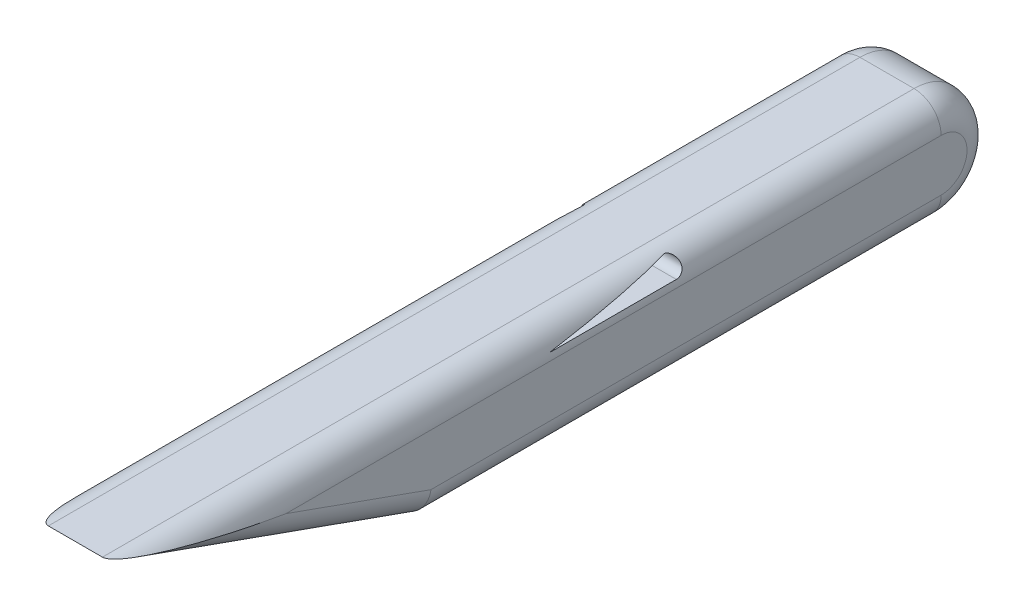
SolidWorks part; units mm, degrees
ref_plane "Front Plane" through (0, 0, 0) normal (0, 0, 1) x (1, 0, 0)
ref_plane "Top Plane" through (0, 0, 0) normal (0, 1, 0) x (1, 0, 0)
ref_plane "Right Plane" through (0, 0, 0) normal (1, 0, 0) x (0, 0, -1)
sketch "Sketch1" plane through (0, 0, 0) normal (1, 0, 0) x (0, 0, -1)
  line L0 (-537.0166, 60.4972) -> (11.6022, -135.0829)
  line L1 (11.6022, -135.0829) -> (962.9834, -135.0829)
  line L2 (-537.0166, 60.4972) -> (962.9834, 60.4972)
  arc A0 (962.9834, 60.4972) -> (962.9834, -135.0829) centre (962.9834, -37.2928) cw
  dimension "D1" = 1500
extrude "Boss-Extrude1" add sketch "Sketch1" against normal mid plane 200 contours A0 L1 L0 L2
fillet "Fillet1" radius 50 8 edges at (-100, -135.0829, -487.2928) (-100, -37.2928, -1060.7735) (100, 60.4972, -212.9834) (100, -37.2928, -1060.7735) (100, -37.2928, 262.7072) (-100, -37.2928, 262.7072) (-100, 60.4972, -212.9834) (100, -135.0829, -487.2928)
sketch "Sketch2" plane through (-100, 0, 0) normal (-1, 0, 0) x (0, 0, 1)
  line L0 (-240.2784, 23.0751) -> (-475.2168, 23.0751) construction
  line L1 (-473.2935, 53.0751) -> (-240.2784, 23.0751) construction
  line L2 (-240.2784, 23.0751) -> (-475.2168, 23.0751)
  line L3 (-473.2935, 53.0751) -> (-240.2784, 23.0751)
  arc A0 (-473.2935, 53.0751) -> (-475.2168, 23.0751) centre (-475.2168, 38.1367) ccw construction
  arc A1 (-473.2935, 53.0751) -> (-475.2168, 23.0751) centre (-475.2168, 38.1367) ccw
extrude "Cut-Extrude1" cut sketch "Sketch2" against normal blind 300
sketch "Sketch3" plane through (0, -135.0829, 0) normal (0, -1, 0) x (1, 0, 0)
  line L0 (50, -962.9834) -> (50, -11.6022) construction
  line L1 (-50, -962.9834) -> (50, -962.9834)
  line L2 (-50, -962.9834) -> (-50, 537.0166)
  line L3 (-50, 537.0166) -> (50, 537.0166)
  line L4 (50, -962.9834) -> (50, 537.0166)
  line L5 (-50, 537.0166) -> (50, 537.0166) construction
extrude "Cut-Extrude2" cut sketch "Sketch3" against normal blind 146 contours L2 L1 L4 L3
